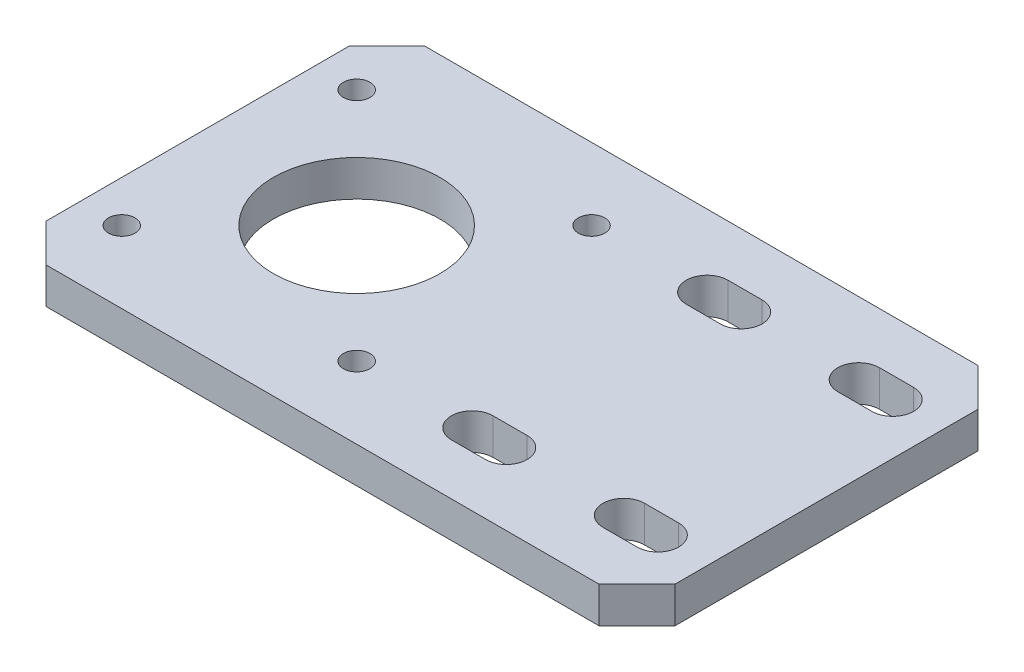
SolidWorks part; units mm, degrees
ref_plane "Front Plane" through (0, 0, 0) normal (0, 0, 1) x (1, 0, 0)
ref_plane "Top Plane" through (0, 0, 0) normal (0, 1, 0) x (1, 0, 0)
ref_plane "Right Plane" through (0, 0, 0) normal (1, 0, 0) x (0, 0, -1)
sketch "Sketch1" plane through (0, 0, 0) normal (0, 1, 0) x (1, 0, 0)
  line L1 (0, 0) -> (83, 0)
  line L2 (0, 0) -> (0, 50)
  line L3 (0, 50) -> (83, 50)
  line L4 (83, 0) -> (83, 50)
  dimension "D1" = 50
  dimension "D2" = 83
extrude "Boss-Extrude1" add sketch "Sketch1" along normal blind 4.7625
sketch "Sketch2" plane through (0, 4.7625, 0) normal (0, 1, 0) x (1, 0, 0)
  line L0 (0, 50) -> (0, 0) construction
  line L1 (83, 50) -> (0, 50) construction
  circle A0 centre (21, 25) radius 11
  circle A1 centre (5.5, 9.5) radius 1.75
  circle A2 centre (36.5, 9.5) radius 1.75
  circle A3 centre (36.5, 40.5) radius 1.75
  circle A4 centre (5.5, 40.5) radius 1.75
  dimension "D1" = 21
  dimension "D3" = 15.5
  dimension "D2" = 25
  dimension "D4" = 15.5
extrude "Cut-Extrude1" cut sketch "Sketch2" against normal through all
sketch "Sketch3" plane through (0, 4.7625, 0) normal (0, 1, 0) x (1, 0, 0)
  line L3 (83, 0) -> (83, 50) construction
  line L4 (83, 25) -> (0, 25) construction
  line L5 (0, 50) -> (0, 0) construction
  line L9 (40, 0) -> (40, 50) construction
  line L10 (83, 50) -> (0, 50) construction
  line L11 (80, 0) -> (80, 50) construction
  circle A4 centre (36.5, 40.5) radius 4 construction
  point P29 (40, 25)
  point P32 (80, 25)
  dimension "D5" = 40
  dimension "D1" = 40
chamfer "Chamfer1" distance 5 angle 45 4 edges at (83, 2.3813, -50) (83, 2.3813, 0) (0, 2.3813, 0) (0, 2.3813, -50)
hole_wizard "M5 Clearance Slot1" positions "Sketch4" profile "Sketch5" size "M5" standard "ANSI Metric" slot yes end condition through all
sketch "Sketch4" plane through (0, 4.7625, 0) normal (0, 1, 0) x (1, 0, 0)
  line L0 (40, 0) -> (40, 50) construction
  line L1 (49, 40.5) -> (59, 40.5) construction
  point P0 (54, 40.5)
  point P13 (74, 40.5)
  point P14 (74, 9.5)
  point P15 (54, 9.5)
  dimension "D1" = 14
  dimension "D2" = 10
  dimension "D3" = 2
  dimension "D4" = 2
sketch "Sketch5" plane through (54, 4.7625, -40.5) normal (1, 0, 0) x (0, 0, 1)
  line L0 (0, 0) -> (0, 4.7625)
  line L1 (0, 4.7625) -> (2.75, 4.7625)
  line L2 (2.75, 4.7625) -> (2.75, 0)
  line L5 (2.75, 0) -> (0, 0)
  line L11 (0, -6.35) -> (0, 107.95) construction
  dimension "Thru Hole Dia." = 5.5
  dimension "Thru Hole Depth" = 4.7625
